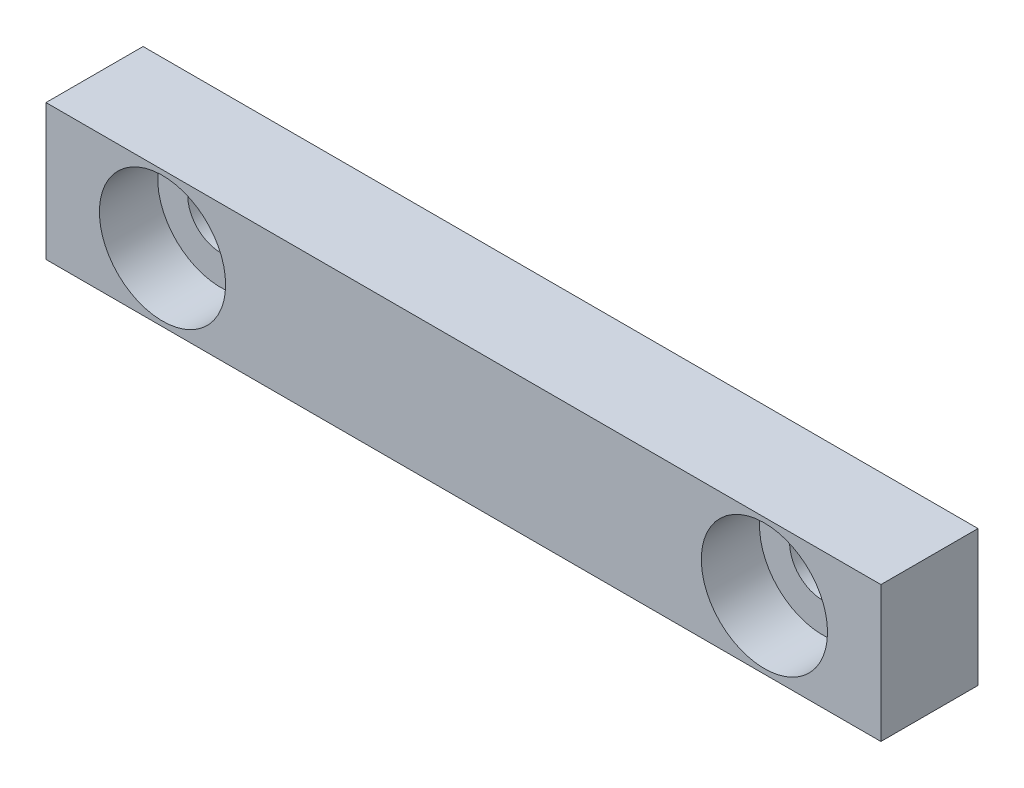
SolidWorks part; units mm, degrees
ref_plane "Front Plane" through (0, 0, 0) normal (0, 0, 1) x (1, 0, 0)
ref_plane "Top Plane" through (0, 0, 0) normal (0, 1, 0) x (1, 0, 0)
ref_plane "Right Plane" through (0, 0, 0) normal (1, 0, 0) x (0, 0, -1)
ref_axis "Axis X" through (-88.99, 0, 0) along (1, 0, 0)
ref_axis "Axis Y" through (0, 55, 0) along (0, -1, 0)
ref_axis "Axis Z" through (0, 0, -88.99) along (0, 0, 1)
sketch "Sketch1" plane through (0, 0, 0) normal (0, 0, 1) x (1, 0, 0)
  line L0 (55, 0) -> (-55, 0) construction
  line L1 (-21.5, 0) -> (21.5, 0)
  line L2 (-21.5, 0) -> (-21.5, 7)
  line L3 (-21.5, 7) -> (21.5, 7)
  line L4 (21.5, 0) -> (21.5, 7)
  line L5 (0, 0) -> (0, 67.1479) construction
  line L6 (0, -55) -> (0, 55) construction
  dimension "D1" = 7
  dimension "D2" = 43
extrude "Boss-Extrude1" add sketch "Sketch1" along normal blind 5
hole_wizard "CBORE for M3 SHCS1" positions "Sketch3" profile "Sketch2" counterbore size "M3" standard "ANSI Metric" end condition through all
sketch "Sketch3" plane through (0, 0, 5) normal (0, 0, 1) x (1, 0, 0)
  line L0 (0, 0) -> (0, -24.2608) construction
  line L2 (-21.5, 3.5) -> (-27.4373, 3.5) construction
  line L3 (-21.5, 7) -> (-21.5, 0) construction
  point P0 (-15.5, 3.5)
  point P2 (15.5, 3.5)
  dimension "D1" = 31
sketch "Sketch2" plane through (-15.5, 3.5, 5) normal (1, 0, 0) x (0, -1, 0)
  line L0 (0, 0) -> (0, 5)
  line L1 (0, 5) -> (1.7, 5)
  line L3 (1.7, 5) -> (1.7, 3)
  line L4 (1.7, 3) -> (3.25, 3)
  line L5 (3.25, 3) -> (3.25, 0)
  line L7 (3.25, 0) -> (0, 0)
  line L11 (0, -6.35) -> (0, 107.95) construction
  dimension "Thru Hole Dia." = 3.4
  dimension "Thru Hole Depth" = 5
  dimension "C'Bore Dia." = 6.5
  dimension "C'Bore Depth" = 3
